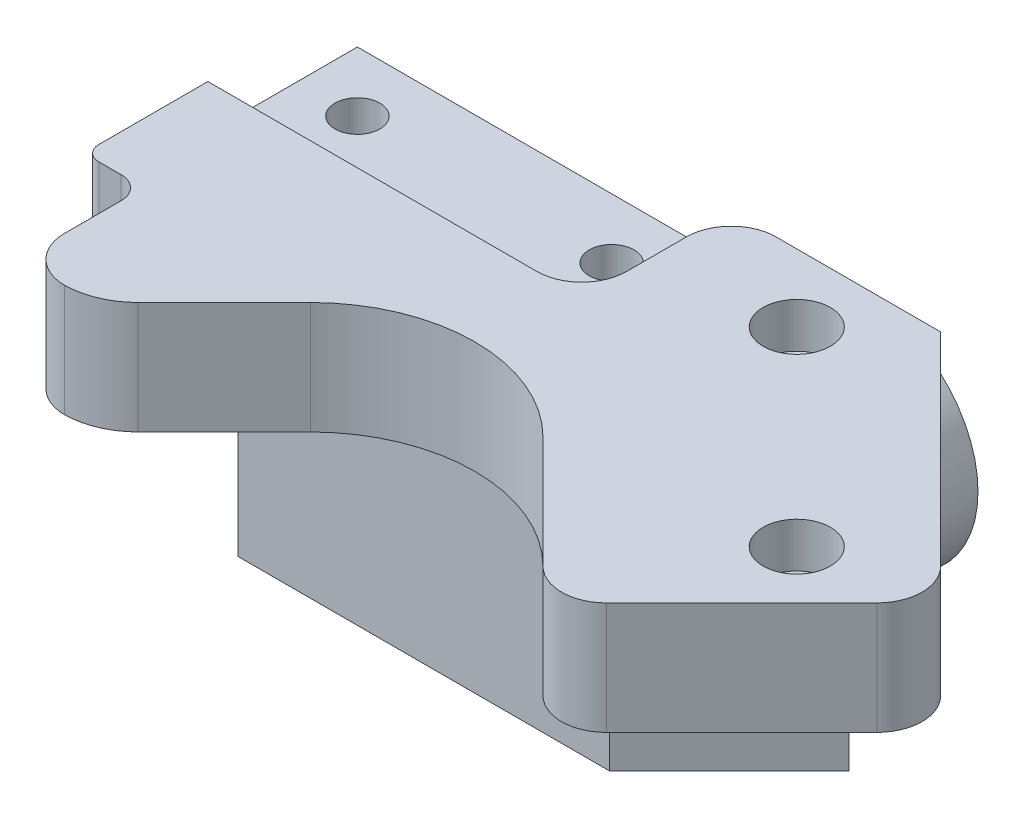
SolidWorks part; units mm, degrees
ref_plane "Front Plane" through (0, 0, 0) normal (0, 0, 1) x (1, 0, 0)
ref_plane "Top Plane" through (0, 0, 0) normal (0, 1, 0) x (1, 0, 0)
ref_plane "Right Plane" through (0, 0, 0) normal (1, 0, 0) x (0, 0, -1)
sketch "Sketch3" plane through (0, 5.4967, 0) normal (0, -1, 0) x (1, 0, 0)
  line L8 (-43.5722, -214.6789) -> (-43.5722, 19.4919) construction
  line L9 (-58.5723, 18.9356) -> (-63.5723, 18.9356)
  line L12 (-35.7941, 11.7137) -> (-26.1725, 21.3353)
  line L13 (-58.5723, 18.9356) -> (-51.3504, 11.7137)
  line L14 (-26.1725, 21.3353) -> (-12.8767, 8.0395)
  line L16 (-28.5722, -7.6561) -> (-12.8767, 8.0395)
  line L17 (-58.5723, -7.6561) -> (-28.5722, -7.6561)
  line L18 (-63.5723, 18.9356) -> (-63.5723, 5.6398)
  line L19 (-43.5722, 19.4919) -> (-32.5722, 19.4919) construction
  line L20 (-58.5723, -7.6561) -> (-63.5723, 5.6398)
  circle A0 centre (-43.5722, 19.4919) radius 11 construction
  arc A2 (-51.3504, 11.7137) -> (-35.7941, 11.7137) centre (-43.5722, 19.4919) ccw
  circle A4 centre (-33.6728, -3.1355) radius 1.5
  circle A5 centre (-20.9448, 9.5924) radius 1.5
extrude "Boss-Extrude1" add sketch "Sketch3" along normal blind 8
sketch "Sketch4" plane through (0, 25.4967, 0) normal (0, 1, 0) x (1, 0, 0)
  line L0 (-67.5734, 21.5545) -> (-67.5734, -11.9295) construction
  line L3 (-65.0723, -10.6398) -> (-67.5734, -10.6398)
  line L4 (-67.5734, 7.6561) -> (-67.5734, -10.6398)
  line L5 (-63.5723, -5.6398) -> (-63.5723, -18.9356)
  line L6 (-63.5723, -12.1398) -> (-63.5723, -18.9356)
  line L10 (-26.1725, -21.3353) -> (-12.8767, -8.0395)
  line L11 (-28.5722, 7.6561) -> (-58.5723, 7.6561)
  line L19 (-28.5722, 7.6561) -> (-67.5734, 7.6561)
  line L21 (-26.1725, -21.3353) -> (-12.8767, -8.0395)
  line L22 (-12.8767, -8.0395) -> (-28.5722, 7.6561)
  line L23 (-12.8767, -8.0395) -> (-28.5722, 7.6561)
  line L26 (-58.5723, 7.6561) -> (-63.5723, -5.6398)
  line L27 (-63.5723, -18.9356) -> (-58.5723, -18.9356)
  line L28 (-63.5723, -18.9356) -> (-58.5723, -18.9356)
  line L29 (-58.5723, -18.9356) -> (-51.3504, -11.7137)
  line L30 (-58.5723, -18.9356) -> (-51.3504, -11.7137)
  line L31 (-35.7941, -11.7137) -> (-26.1725, -21.3353)
  line L32 (-35.7941, -11.7137) -> (-26.1725, -21.3353)
  arc A1 (-35.7941, -11.7137) -> (-51.3504, -11.7137) centre (-43.5722, -19.4919) ccw
  arc A2 (-35.7941, -11.7137) -> (-51.3504, -11.7137) centre (-43.5722, -19.4919) ccw
  arc A3 (-63.5723, -12.1398) -> (-65.0723, -10.6398) centre (-65.0723, -12.1398) ccw
  dimension "D3" = 1.5
  dimension "D1" = 0
extrude "Boss-Extrude2" add sketch "Sketch4" along normal blind 8 separate body
sketch "Sketch9" plane through (0, 25.4967, 0) normal (0, -1, 0) x (1, 0, 0)
  line L0 (-34.7096, -7.6561) -> (-42.7096, 0.3439)
  line L2 (-42.7096, 0.3439) -> (-58.4567, 0.3439)
  line L3 (-34.7096, -7.6561) -> (-58.4567, -7.6561)
  line L4 (-58.4567, -7.6561) -> (-58.4567, 0.3439)
  line L6 (-58.5723, -7.6561) -> (-28.5722, -7.6561) construction
  line L7 (-20.9448, 9.5924) -> (-33.6728, -3.1355) construction
  dimension "D1" = 8
extrude "Boss-Extrude3" add sketch "Sketch9" along normal up to surface (20 mm away) up to face at (-44.3395, 5.4967, 8.6421)
sketch "Sketch10" plane through (0, 0, -7.6561) normal (0, 0, -1) x (-1, 0, 0)
  circle A0 centre (43.5723, 15.4967) radius 5
  circle A1 centre (43.5723, 15.4967) radius 7.5
extrude "Boss-Extrude4" add sketch "Sketch10" along normal blind 10
fillet "Fillet1" radius 3 6 edges at (-26.1725, 29.4967, 21.3353) (-12.8767, 29.4967, 8.0395) (-26.1725, 1.4967, 21.3353) (-12.8767, 1.4967, 8.0395) (-63.5723, 29.4967, 18.9356) (-63.5723, 1.4967, 18.9356)
sketch "Sketch11" plane through (0, 25.4967, 0) normal (0, -1, 0) x (1, 0, 0)
  line L12 (-58.5723, 18.9356) -> (-60.5723, 18.9356)
  line L13 (-63.5723, 15.9356) -> (-63.5723, 12.1398)
  line L15 (-67.5734, -7.6561) -> (-58.4567, -7.6561)
  line L16 (-58.4567, -7.6561) -> (-58.4567, 0.3439)
  line L17 (-58.4567, 0.3439) -> (-42.7096, 0.3439)
  line L18 (-42.7096, 0.3439) -> (-34.7096, -7.6561)
  line L19 (-34.7096, -7.6561) -> (-28.5722, -7.6561)
  line L20 (-28.5722, -7.6561) -> (-14.998, 5.9181)
  line L21 (-14.998, 10.1608) -> (-24.0512, 19.214)
  line L22 (-28.2939, 19.214) -> (-35.7941, 11.7137)
  line L23 (-51.3504, 11.7137) -> (-58.5723, 18.9356)
  line L24 (-58.5723, 18.9356) -> (-60.5723, 18.9356)
  line L25 (-63.5723, 15.9356) -> (-63.5723, 12.1398)
  line L27 (-67.5734, -7.6561) -> (-58.4567, -7.6561)
  line L28 (-58.4567, -7.6561) -> (-58.4567, 0.3439)
  line L29 (-58.4567, 0.3439) -> (-42.7096, 0.3439)
  line L30 (-42.7096, 0.3439) -> (-34.7096, -7.6561)
  line L31 (-34.7096, -7.6561) -> (-28.5722, -7.6561)
  line L32 (-28.5722, -7.6561) -> (-14.998, 5.9181)
  line L33 (-14.998, 10.1608) -> (-24.0512, 19.214)
  line L34 (-28.2939, 19.214) -> (-35.7941, 11.7137)
  line L35 (-51.3504, 11.7137) -> (-58.5723, 18.9356)
  line L39 (-65.0723, 10.6398) -> (-67.5734, 10.6398)
  line L40 (-65.0723, 10.6398) -> (-67.5734, 10.6398)
  line L41 (-67.5734, 10.6398) -> (-67.5734, -7.6561)
  line L42 (-67.5734, 10.6398) -> (-67.5734, -7.6561)
  arc A4 (-60.5723, 18.9356) -> (-63.5723, 15.9356) centre (-60.5723, 15.9356) ccw
  arc A5 (-14.998, 5.9181) -> (-14.998, 10.1608) centre (-17.1193, 8.0395) ccw
  arc A6 (-24.0512, 19.214) -> (-28.2939, 19.214) centre (-26.1725, 17.0926) ccw
  arc A7 (-51.3504, 11.7137) -> (-35.7941, 11.7137) centre (-43.5722, 19.4919) ccw
  arc A8 (-60.5723, 18.9356) -> (-63.5723, 15.9356) centre (-60.5723, 15.9356) ccw
  arc A9 (-14.998, 5.9181) -> (-14.998, 10.1608) centre (-17.1193, 8.0395) ccw
  arc A10 (-24.0512, 19.214) -> (-28.2939, 19.214) centre (-26.1725, 17.0926) ccw
  arc A11 (-51.3504, 11.7137) -> (-35.7941, 11.7137) centre (-43.5722, 19.4919) ccw
  arc A14 (-65.0723, 10.6398) -> (-63.5723, 12.1398) centre (-65.0723, 12.1398) ccw
  arc A15 (-65.0723, 10.6398) -> (-63.5723, 12.1398) centre (-65.0723, 12.1398) ccw
  dimension "D1" = 0
extrude "Cut-Extrude1" cut sketch "Sketch11" against normal blind 0.5
sketch "Sketch12" plane through (0, 5.4967, 0) normal (0, 1, 0) x (1, 0, 0)
  line L0 (-67.5734, -10.6398) -> (-65.0723, -10.6398) construction
  line L1 (-67.5734, 7.6561) -> (-67.5734, -10.6398) construction
  line L3 (-67.5734, -10.6398) -> (-65.0723, -10.6398)
  line L4 (-67.5734, 7.6561) -> (-67.5734, -10.6398)
  line L5 (-65.6492, -5.6398) -> (-67.5734, 7.6561)
  line L12 (-63.5723, -5.6398) -> (-63.5723, -15.9356)
  line L13 (-60.5723, -18.9356) -> (-58.5723, -18.9356)
  line L14 (-58.5723, -18.9356) -> (-51.3504, -11.7137)
  line L15 (-35.7941, -11.7137) -> (-28.2939, -19.214)
  line L16 (-24.0512, -19.214) -> (-14.998, -10.1608)
  line L17 (-14.998, -5.9181) -> (-28.5722, 7.6561)
  line L18 (-28.5722, 7.6561) -> (-34.7096, 7.6561)
  line L19 (-34.7096, 7.6561) -> (-42.7096, -0.3439)
  line L20 (-42.7096, -0.3439) -> (-58.4567, -0.3439)
  line L21 (-58.4567, -0.3439) -> (-58.4567, 7.6561)
  line L22 (-58.4567, 7.6561) -> (-58.5723, 7.6561)
  line L23 (-58.5723, 7.6561) -> (-63.5723, -5.6398)
  line L24 (-63.5723, -12.1398) -> (-63.5723, -15.9356)
  line L25 (-60.5723, -18.9356) -> (-58.5723, -18.9356)
  line L26 (-58.5723, -18.9356) -> (-51.3504, -11.7137)
  line L27 (-35.7941, -11.7137) -> (-28.2939, -19.214)
  line L28 (-24.0512, -19.214) -> (-14.998, -10.1608)
  line L29 (-14.998, -5.9181) -> (-28.5722, 7.6561)
  line L30 (-28.5722, 7.6561) -> (-34.7096, 7.6561)
  line L31 (-34.7096, 7.6561) -> (-42.7096, -0.3439)
  line L32 (-42.7096, -0.3439) -> (-58.4567, -0.3439)
  line L33 (-58.4567, -0.3439) -> (-58.4567, 7.6561)
  line L34 (-58.4567, 7.6561) -> (-58.5723, 7.6561)
  line L35 (-58.5723, 7.6561) -> (-62.8412, -3.6957)
  arc A0 (-65.6492, -5.6398) -> (-62.8412, -3.6957) centre (-65.6492, -2.6398) ccw
  arc A1 (-65.0723, -10.6398) -> (-63.5723, -12.1398) centre (-65.0723, -12.1398) cw
  arc A4 (-63.5723, -15.9356) -> (-60.5723, -18.9356) centre (-60.5723, -15.9356) ccw
  arc A5 (-35.7941, -11.7137) -> (-51.3504, -11.7137) centre (-43.5722, -19.4919) ccw
  arc A6 (-28.2939, -19.214) -> (-24.0512, -19.214) centre (-26.1725, -17.0926) ccw
  arc A7 (-14.998, -10.1608) -> (-14.998, -5.9181) centre (-17.1193, -8.0395) ccw
  arc A8 (-63.5723, -15.9356) -> (-60.5723, -18.9356) centre (-60.5723, -15.9356) ccw
  arc A9 (-35.7941, -11.7137) -> (-51.3504, -11.7137) centre (-43.5722, -19.4919) ccw
  arc A10 (-28.2939, -19.214) -> (-24.0512, -19.214) centre (-26.1725, -17.0926) ccw
  arc A11 (-14.998, -10.1608) -> (-14.998, -5.9181) centre (-17.1193, -8.0395) ccw
  dimension "D1" = 0
extrude "Cut-Extrude2" cut sketch "Sketch12" against normal blind 0.5
chamfer "Chamfer1" distance 3 angle 45 1 edges at (-36.0723, 15.4967, -7.6561)
sketch "Sketch13" plane through (0, 25.9967, 0) normal (0, -1, 0) x (1, 0, 0)
  line L0 (-58.4567, -7.6561) -> (-58.4567, 0.3439) construction
  line L2 (-58.4567, -7.6561) -> (-58.4567, 0.3439)
  line L3 (-67.5734, 0.3439) -> (-67.5734, -7.6561)
  line L4 (-58.4567, 0.3439) -> (-67.5734, 0.3439)
  line L5 (-67.5734, -7.6561) -> (-58.4567, -7.6561) construction
  line L6 (-67.5734, -7.6561) -> (-58.4567, -7.6561)
  line L7 (-67.5734, -21.5548) -> (-67.5734, 11.9292) construction
extrude "Boss-Extrude5" add sketch "Sketch13" along normal up to surface (21 mm away) up to face at (-22.4448, 4.9967, 9.5924)
fillet "Fillet2" radius 15 1 edges at (-63.5723, 1.2467, 5.6398)
fillet "Fillet3" radius 5 2 edges at (-58.5723, 29.7467, 18.9356) (-58.5723, 1.2467, 18.9356)
sketch "Sketch14" plane through (0, -2.5033, 0) normal (0, -1, 0) x (1, 0, 0)
  line L10 (-62.6123, 3.0871) -> (-58.5723, -7.6561) construction
  line L11 (-63.5723, 15.9356) -> (-63.5723, 8.367) construction
  line L12 (-62.6123, 3.0871) -> (-58.5723, -7.6561)
  line L13 (-63.5723, 12.1398) -> (-63.5723, 8.367)
  line L19 (-67.5734, -7.6561) -> (-28.5722, -7.6561)
  line L20 (-28.5722, -7.6561) -> (-12.8767, 8.0395)
  line L21 (-12.8767, 8.0395) -> (-26.1725, 21.3353)
  line L22 (-26.1725, 21.3353) -> (-35.7941, 11.7137)
  line L23 (-51.3504, 11.7137) -> (-58.5723, 18.9356)
  line L24 (-58.5723, 18.9356) -> (-63.5723, 18.9356)
  line L25 (-63.5723, 18.9356) -> (-63.5723, 12.1398)
  line L26 (-65.0723, 10.6398) -> (-67.5734, 10.6398)
  line L27 (-67.5734, 10.6398) -> (-67.5734, -7.6561)
  line L28 (-67.5734, -7.6561) -> (-58.5723, -7.6561)
  line L35 (-65.0723, 10.6398) -> (-67.5734, 10.6398)
  line L36 (-67.5734, 10.6398) -> (-67.5734, -7.6561)
  arc A6 (-63.5723, 8.367) -> (-62.6123, 3.0871) centre (-48.5723, 8.367) ccw construction
  arc A7 (-63.5723, 8.367) -> (-62.6123, 3.0871) centre (-48.5723, 8.367) ccw
  arc A8 (-51.3504, 11.7137) -> (-35.7941, 11.7137) centre (-43.5722, 19.4919) ccw
  arc A9 (-65.0723, 10.6398) -> (-63.5723, 12.1398) centre (-65.0723, 12.1398) ccw
  arc A11 (-65.0723, 10.6398) -> (-63.5723, 12.1398) centre (-65.0723, 12.1398) ccw
  dimension "D1" = 0
extrude "Boss-Extrude6" add sketch "Sketch14" against normal up to surface (7.5 mm away) up to face at (-22.4448, 4.9967, 9.5924)
sketch "Sketch15" plane through (0, -2.5033, 0) normal (0, -1, 0) x (1, 0, 0)
  line L0 (-67.5734, -7.6561) -> (-28.5722, -7.6561) construction
  line L1 (-67.5734, 2.3439) -> (-42.5734, 2.3439)
  line L2 (-67.5734, 2.3439) -> (-67.5734, -7.6561)
  line L3 (-67.5734, -7.6561) -> (-42.5734, -7.6561)
  line L4 (-42.5734, 2.3439) -> (-42.5734, -7.6561)
extrude "Cut-Extrude3" cut sketch "Sketch15" against normal blind 3
sketch "Sketch17" plane through (0, 33.4967, 0) normal (0, 1, 0) x (1, 0, 0)
  line L4 (-67.5734, 7.6561) -> (-67.5734, -2.3439)
  line L5 (-42.5734, 7.6561) -> (-67.5734, 7.6561)
  line L6 (-42.5734, -2.3439) -> (-42.5734, 7.6561)
  line L7 (-67.5734, -2.3439) -> (-42.5734, -2.3439)
  line L8 (-67.5734, 7.6561) -> (-67.5734, -2.3439)
  line L9 (-42.5734, 7.6561) -> (-67.5734, 7.6561)
  line L10 (-42.5734, -2.3439) -> (-42.5734, 7.6561)
  line L11 (-67.5734, -2.3439) -> (-42.5734, -2.3439)
  dimension "D1" = 0
extrude "Cut-Extrude4" cut sketch "Sketch17" against normal blind 3
fillet "Fillet4" radius 3 4 edges at (-42.5734, 31.9967, 2.3439) (-42.5734, 31.9967, -7.6561) (-42.5734, -1.0033, 2.3439) (-42.5734, -1.0033, -7.6561)
sketch "Sketch18" plane through (0, -2.5033, 0) normal (0, -1, 0) x (1, 0, 0)
  circle A0 centre (-46.5734, -3.6561) radius 1.5
  circle A1 centre (-63.5734, -3.6561) radius 1.5
extrude "Cut-Extrude5" cut sketch "Sketch18" against normal up to surface (36 mm away) up to face at (-45.1492, 33.4967, 8.1147)
sketch "Sketch20" plane through (0, -2.5033, 0) normal (0, -1, 0) x (1, 0, 0)
  line L1 (-12.2781, 24.9771) -> (-73.2595, 24.9771)
  line L2 (-12.2781, 24.9771) -> (-12.2781, -21.2101)
  line L3 (-12.2781, -21.2101) -> (-73.2595, -21.2101)
  line L4 (-73.2595, 24.9771) -> (-73.2595, -21.2101)
extrude "Cut-Extrude6" cut sketch "Sketch20" against normal up to surface (7.5 mm away) up to face at (-44.9881, 4.9967, 9.2111)
sketch "Sketch21" plane through (0, 25.9967, 0) normal (0, -1, 0) x (1, 0, 0)
  circle A0 centre (-20.9448, 9.5924) radius 1.5
  circle A1 centre (-33.6728, -3.1355) radius 1.5
extrude "Cut-Extrude7" cut sketch "Sketch21" against normal up to surface (7.5 mm away) up to face at (-45.1492, 33.4967, 8.1147)
sketch "Sketch22" plane through (0, 33.4967, 0) normal (0, 1, 0) x (1, 0, 0)
  circle A0 centre (-20.9448, -9.5924) radius 2.25
  circle A1 centre (-33.6728, 3.1355) radius 2.25
extrude "Cut-Extrude8" cut sketch "Sketch22" against normal blind 3
fillet "Fillet5" radius 1 1 edges at (-67.5734, 29.7467, 10.6398)
